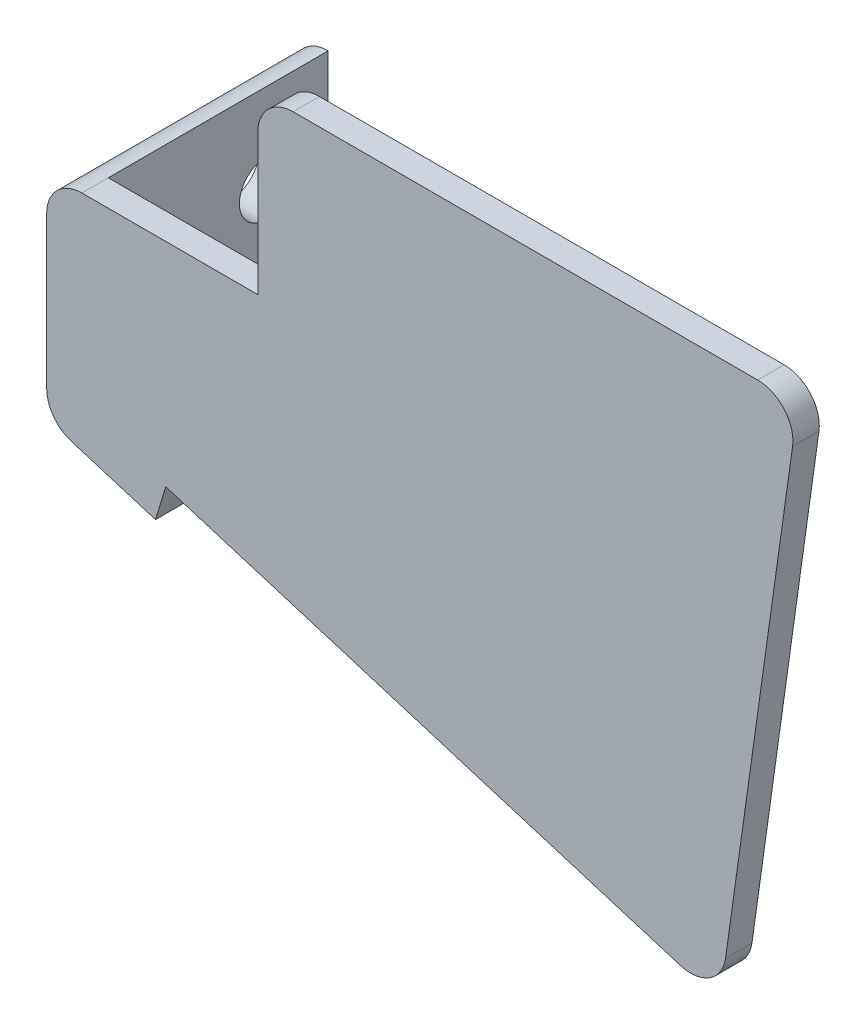
SolidWorks part; units mm, degrees
material "POLYURETHANE (11671)"
ref_plane "Front Plane" through (0, 0, 0) normal (0, 0, 1) x (1, 0, 0)
ref_plane "Top Plane" through (0, 0, 0) normal (0, 1, 0) x (1, 0, 0)
ref_plane "Right Plane" through (0, 0, 0) normal (1, 0, 0) x (0, 0, -1)
sketch "Sketch1" plane through (0, 0, 0) normal (0, 0, 1) x (1, 0, 0)
  line L5 (-6.1517, -2.7255) -> (24.5549, -2.7255)
  line L9 (20.1005, -34.4204) -> (24.5549, -2.7255)
  line L16 (-18.1517, -22.7255) -> (20.1005, -34.4204)
  line L17 (-18.1517, -12.7255) -> (-18.1517, -22.7255)
  line L21 (-18.1517, -12.7255) -> (-6.1517, -12.7255)
  line L22 (-6.1517, -2.7255) -> (-6.1517, -12.7255)
  dimension "D1" = 107
  dimension "D4" = 82
  dimension "D2" = 40
  dimension "D3" = 12
extrude "Boss-Extrude1" add sketch "Sketch1" along normal blind 1.5
sketch "Sketch5" plane through (0, 0, 1.5) normal (0, 0, 1) x (1, 0, 0)
  line L0 (-16.1517, -23.337) -> (-11.3837, -24.7947)
  line L1 (-18.1517, -12.7255) -> (-16.1517, -12.7255)
  line L2 (-18.1517, -12.7255) -> (-18.1517, -24.8169)
  line L4 (-16.1517, -12.7255) -> (-16.1517, -23.337)
  line L5 (-11.3837, -24.7947) -> (-11.9684, -26.7073)
  line L6 (-11.9684, -26.7073) -> (-18.1517, -24.8169)
  line L7 (-18.1517, -22.7255) -> (20.1005, -34.4204) construction
  point P9 (0, 0)
  dimension "D1" = 2
  dimension "D2" = 2
extrude "Boss-Extrude3" add sketch "Sketch5" against normal blind 14
sketch "Sketch6" plane through (-16.1517, 0, 0) normal (1, 0, 0) x (0, 0, -1)
  line L0 (0, -23.337) -> (0, -12.7255) construction
  line L1 (12.5, -12.7255) -> (0, -12.7255) construction
  circle A0 centre (9, -17.7255) radius 1.55
  dimension "D1" = 3.1
  dimension "D2" = 9
  dimension "D3" = 5
extrude "Cut-Extrude1" cut sketch "Sketch6" against normal blind 14
fillet "Fillet1" radius 2 6 edges at (-18.1517, -12.7255, -5.5) (-11.3837, -24.7947, -6.25) (-18.1517, -24.8169, -5.5) (20.1005, -34.4204, 0.75) (-6.1517, -2.7255, 0.75) (24.5549, -2.7255, 0.75)
